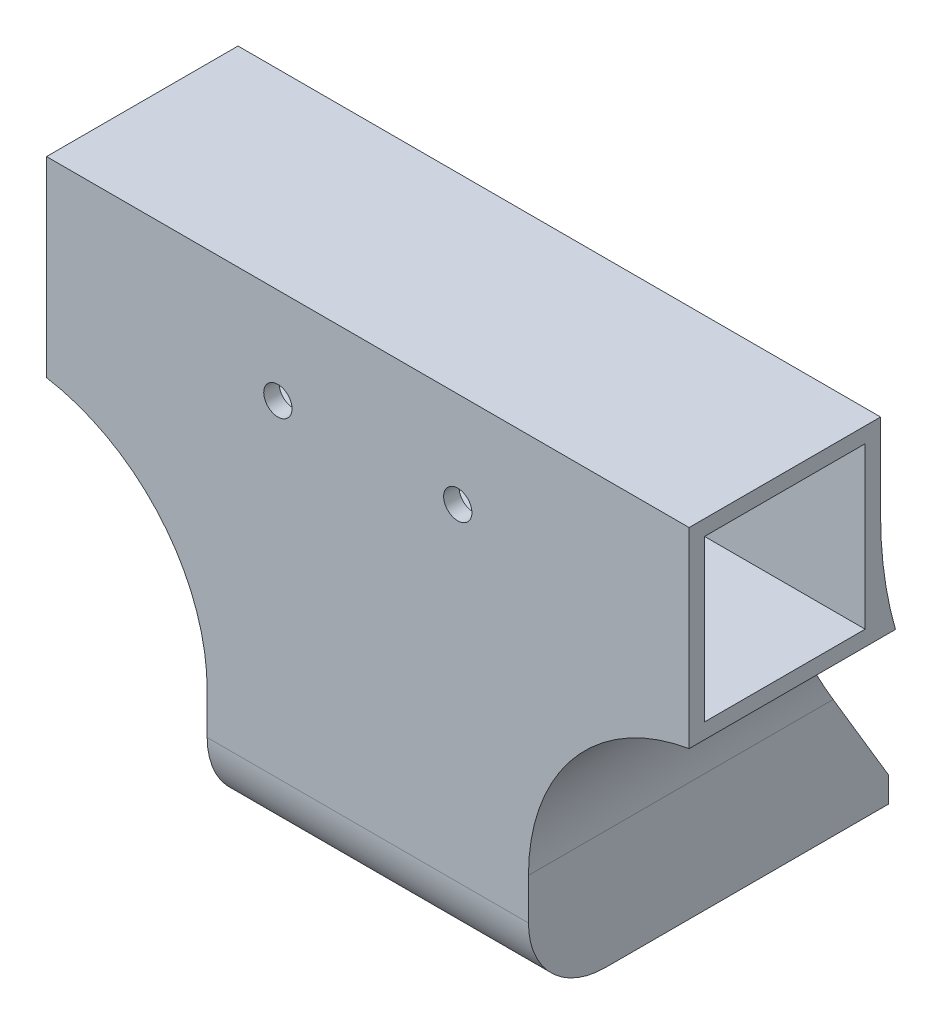
SolidWorks part; units mm, degrees
ref_plane "Front" through (0, 0, 0) normal (0, 0, 1) x (1, 0, 0)
ref_plane "Top" through (0, 0, 0) normal (0, 1, 0) x (1, 0, 0)
ref_plane "Right" through (0, 0, 0) normal (1, 0, 0) x (0, 0, -1)
sketch "Эскиз1" plane through (0, 0, 0) normal (1, 0, 0) x (0, 0, -1)
  line L1 (-12.5, -12.5) -> (12.5, -12.5)
  line L2 (-12.5, -12.5) -> (-12.5, 12.5)
  line L3 (-12.5, 12.5) -> (12.5, 12.5)
  line L4 (12.5, -12.5) -> (12.5, 12.5)
  line L5 (-12.5, -12.5) -> (12.5, 12.5) construction
  line L6 (-12.5, 12.5) -> (12.5, -12.5) construction
  point P0 (0, 0)
  dimension "D1" = 25
  dimension "D2" = 25
extrude "Вытянуть-Тонкостенный1" add sketch "Эскиз1" along normal blind 100 thin thin type one direction wall 2.4
sketch "Эскиз2" plane through (0, -14.9, 0) normal (0, -1, 0) x (1, 0, 0)
  line L0 (50, 14.9) -> (50, -14.9) construction
  line L1 (100, 14.9) -> (0, 14.9) construction
  line L2 (100, -14.9) -> (0, -14.9) construction
  line L4 (25, 0.9) -> (75, 0.9)
  line L5 (25, 0.9) -> (25, 14.9)
  line L6 (25, 14.9) -> (75, 14.9)
  line L7 (75, 0.9) -> (75, 14.9)
  line L8 (25, 0.9) -> (75, 14.9) construction
  line L9 (25, 14.9) -> (75, 0.9) construction
  point P6 (50, 7.9)
  dimension "D1" = 50
  dimension "D2" = 14
extrude "Бобышка-Вытянуть1" add sketch "Эскиз2" along normal blind 48
sketch "Эскиз3" plane through (0, 0, 0.9) normal (0, 0, -1) x (-1, 0, 0)
  line L0 (-25, -62.9) -> (-25, -14.9) construction
  line L1 (-75, -62.9) -> (-25, -62.9)
  line L2 (-75, -62.9) -> (-75, -58.9)
  line L3 (-75, -58.9) -> (-25, -58.9)
  line L4 (-25, -62.9) -> (-25, -58.9)
  dimension "D1" = 4
extrude "Бобышка-Вытянуть2" add sketch "Эскиз3" along normal blind 42
sketch "Эскиз4" plane through (75, 0, 0) normal (1, 0, 0) x (0, 0, -1)
  line L0 (14.9, -14.9) -> (41.1, -58.9)
  line L1 (41.1, -58.9) -> (-0.9, -58.9)
  line L2 (-0.9, -58.9) -> (-0.9, -14.9)
  line L3 (-0.9, -14.9) -> (14.9, -14.9)
extrude "Бобышка-Вытянуть3" add sketch "Эскиз4" against normal blind 4
sketch "Эскиз5" plane through (25, 0, 0) normal (-1, 0, 0) x (0, 0, 1)
  line L0 (-41.1, -58.9) -> (-14.9, -14.9)
  line L1 (-14.9, -14.9) -> (0.9, -14.9)
  line L2 (0.9, -14.9) -> (0.9, -58.9)
  line L3 (0.9, -58.9) -> (-41.1, -58.9)
extrude "Бобышка-Вытянуть4" add sketch "Эскиз5" against normal blind 4
fillet "Скругление2" radius 30 2 edges at (75, -14.9, 0) (25, -14.9, 0)
sketch "Эскиз6" plane through (0, -62.9, 0) normal (0, -1, 0) x (1, 0, 0)
  line L0 (50, 14.9) -> (50, -41.1) construction
  line L1 (75, 14.9) -> (25, 14.9) construction
  line L2 (75, -41.1) -> (25, -41.1) construction
  line L4 (34.5, -35.6) -> (65.5, -35.6) construction
  line L5 (34.5, -35.6) -> (34.5, -4.6) construction
  line L6 (34.5, -4.6) -> (65.5, -4.6) construction
  line L7 (65.5, -35.6) -> (65.5, -4.6) construction
  line L8 (34.5, -35.6) -> (65.5, -4.6) construction
  line L9 (34.5, -4.6) -> (65.5, -35.6) construction
  circle A0 centre (50, -20.1) radius 11.5
  circle A1 centre (34.5, -4.6) radius 1.6
  circle A2 centre (65.5, -4.6) radius 1.6
  circle A3 centre (34.5, -35.6) radius 1.6
  circle A4 centre (65.5, -35.6) radius 1.6
  dimension "D1" = 31
  dimension "D3" = 35
  dimension "D2" = 31
extrude "Вырез-Вытянуть1" cut sketch "Эскиз6" against normal up to next
fillet "Скругление3" radius 12 1 edges at (50, -62.9, 14.9)
fillet "Скругление4" radius 60 2 edges at (14.5, -14.9, -14.9) (85.5, -14.9, -14.9)
sketch "Эскиз7" plane through (0, 0, -14.9) normal (0, 0, -1) x (-1, 0, 0)
  line L0 (0, 0) -> (-100, 0) construction
  line L1 (-100, 1.6109) -> (-100, -14.9) construction
  line L2 (-100, 1.6109) -> (-100, 14.9) construction
  line L3 (0, 1.6109) -> (0, 14.9) construction
  circle A0 centre (-64, 0) radius 2.2
  circle A1 centre (-36, 0) radius 2.2
  dimension "D1" = 36
  dimension "D2" = 36
extrude "Вырез-Вытянуть2" cut sketch "Эскиз7" against normal through all
fillet "Скругление5" radius 2 1 edges at (50, -14.9, -14.9)
sketch "Эскиз8" plane through (25, 0, 0) normal (-1, 0, 0) x (0, 0, 1)
  line L0 (2.9, -62.9) -> (-41.1, -62.9) construction
  line L1 (-41.1, -62.9) -> (-41.1, -58.9) construction
  circle A0 centre (-25.1, -60.9) radius 1.2
  circle A1 centre (2.9, -60.9) radius 1.2
  dimension "D1" = 28
  dimension "D2" = 2
  dimension "D3" = 16
extrude "Вырез-Вытянуть3" cut sketch "Эскиз8" against normal blind 5
sketch "Эскиз9" plane through (25, 0, 0) normal (-1, 0, 0) x (0, 0, 1)
  line L0 (2.9, -62.9) -> (-41.1, -62.9) construction
  line L1 (-27.3361, -62.9) -> (-22.8639, -62.9)
  line L2 (2.9, -62.9) -> (0.6464, -62.9)
  arc A0 (-22.8639, -62.9) -> (-27.3361, -62.9) centre (-25.1, -60.9) ccw
  arc A1 (5.5135, -62.3995) -> (0.6464, -62.9) centre (2.9, -60.9) ccw
  circle A3 centre (-25.1, -60.9) radius 1.2
  circle A4 centre (2.9, -60.9) radius 1.2
  arc A5 (2.9, -62.9) -> (5.5135, -62.3995) centre (-0.2425, -39.4183) ccw
  point P14 (5.5135, -62.3995)
extrude "Бобышка-Вытянуть5" add sketch "Эскиз9" along normal blind 1
fillet "Скругление6" radius 1 2 edges at (25, -57.9027, 2.5918) (25, -57.9, -25.1)
